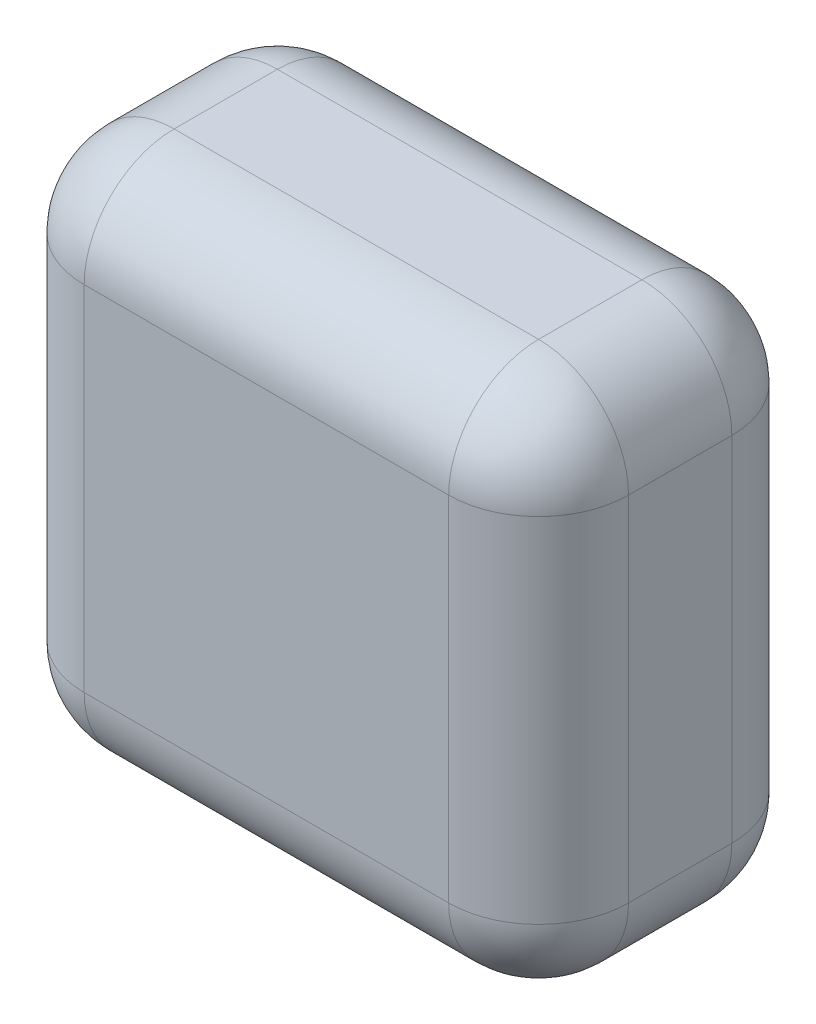
SolidWorks part; units mm, degrees
ref_plane "Front Plane" through (0, 0, 0) normal (0, 0, 1) x (1, 0, 0)
ref_plane "Top Plane" through (0, 0, 0) normal (0, 1, 0) x (1, 0, 0)
ref_plane "Right Plane" through (0, 0, 0) normal (1, 0, 0) x (0, 0, -1)
sketch "Sketch1" plane through (0, 0, 0) normal (0, 1, 0) x (1, 0, 0)
  line L1 (0, 0) -> (-101.0582, 0)
  line L2 (0, 0) -> (0, 42.9713)
  line L3 (0, 42.9713) -> (-101.0582, 42.9713)
  line L4 (-101.0582, 0) -> (-101.0582, 42.9713)
extrude "Boss-Extrude1" add sketch "Sketch1" along normal blind 68.58 and the other way blind 29.972
fillet "Fillet1" radius 10 12 edges at (0, 19.304, 0) (-50.5291, -29.972, 0) (-101.0582, 19.304, -42.9713) (-50.5291, 68.58, -42.9713) (0, 19.304, -42.9713) (-50.5291, -29.972, -42.9713) (-101.0582, -29.972, -21.4857) (0, -29.972, -21.4857) (0, 68.58, -21.4857) (-101.0582, 68.58, -21.4857) (-101.0582, 19.304, 0) (-50.5291, 68.58, 0)
shell "Shell3" thickness 10 removed face at (-50.5291, 19.304, -42.9713) outward yes
